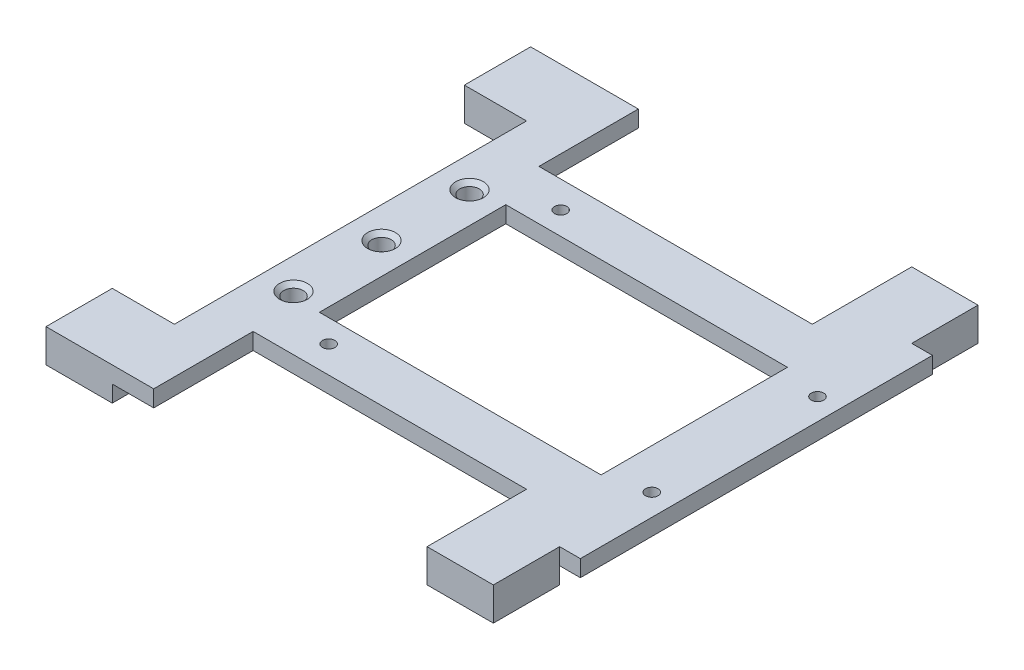
SolidWorks part; units mm, degrees
ref_plane "Front Plane" through (0, 0, 0) normal (0, 0, 1) x (1, 0, 0)
ref_plane "Top Plane" through (0, 0, 0) normal (0, 1, 0) x (1, 0, 0)
ref_plane "Right Plane" through (0, 0, 0) normal (1, 0, 0) x (0, 0, -1)
sketch "Sketch1" plane through (0, 0, 0) normal (0, 1, 0) x (1, 0, 0)
  line L1 (-56.5, 42.5) -> (56.5, 42.5)
  line L2 (-56.5, 42.5) -> (-56.5, -42.5)
  line L3 (-56.5, -42.5) -> (56.5, -42.5)
  line L4 (56.5, 42.5) -> (56.5, -42.5)
  line L5 (-56.5, 42.5) -> (56.5, -42.5) construction
  line L6 (-56.5, -42.5) -> (56.5, 42.5) construction
  point P0 (0, 0)
  dimension "D1" = 113
  dimension "D2" = 85
extrude "Boss-Extrude1" add sketch "Sketch1" along normal blind 4
sketch "Sketch2" plane through (0, 4, 0) normal (0, 1, 0) x (1, 0, 0)
  line L0 (0, 42.5) -> (0, -42.5) construction
  line L1 (56.5, 42.5) -> (-56.5, 42.5) construction
  line L2 (-56.5, -42.5) -> (56.5, -42.5) construction
  line L4 (-56.5, 0) -> (56.5, 0) construction
  line L5 (-56.5, 42.5) -> (-56.5, -42.5) construction
  line L6 (56.5, -42.5) -> (56.5, 42.5) construction
  circle A46 centre (-18.75, 28) radius 1.5
  circle A47 centre (-18.75, -28) radius 1.5
  circle A48 centre (51.25, -20) radius 1.5
  circle A49 centre (51.25, 20) radius 1.5
  point P20 (22.5, 0)
  line B0 (-25.4814, 0) -> (70.4814, 0) construction
  arc B1 (-19.5394, -30.8943) -> (-19.2077, -30.9649) centre (-18.75, -28) ccw construction
  arc B2 (-21.6443, -28.7894) -> (-19.5394, -30.8943) centre (-18.75, -28) ccw construction
  arc B3 (-21.7149, -28.4577) -> (-21.6443, -28.7894) centre (-18.75, -28) ccw construction
  arc B4 (-19.2077, 30.9649) -> (-19.5394, 30.8943) centre (-18.75, 28) ccw construction
  arc B5 (-19.5394, 30.8943) -> (-21.6443, 28.7894) centre (-18.75, 28) ccw construction
  arc B6 (-21.6443, 28.7894) -> (-21.7149, 28.4577) centre (-18.75, 28) ccw construction
  arc B7 (-21.7149, 28.4577) -> (-21.7149, -28.4577) centre (83.9083, 0) ccw construction
  arc B8 (-19.2077, -30.9649) -> (9.25, -34.7314) centre (9.25, 74.6583) ccw construction
  arc B9 (9.25, -34.7314) -> (63.3655, -15.1715) centre (9.25, 49.9083) ccw construction
  arc B10 (63.3655, -15.1715) -> (63.3655, 15.1715) centre (50.75, 0) ccw construction
  arc B11 (63.3655, 15.1715) -> (9.25, 34.7314) centre (9.25, -49.9083) ccw construction
  arc B12 (9.25, 34.7314) -> (-19.2077, 30.9649) centre (9.25, -74.6583) ccw construction
  arc B13 (51.25, 22.5132) -> (51.25, 17.4868) centre (51.25, 20) ccw construction
  arc B14 (51.25, 17.5) -> (51.25, 22.5) centre (51.25, 20) ccw construction
  arc B15 (51.25, -17.5) -> (51.25, -22.5) centre (51.25, -20) ccw construction
  arc B16 (51.25, -22.5132) -> (51.25, -17.4868) centre (51.25, -20) ccw construction
  arc B17 (-18.75, -25.5) -> (-18.75, -30.5) centre (-18.75, -28) ccw construction
  arc B18 (-18.75, -30.5132) -> (-18.75, -25.4868) centre (-18.75, -28) ccw construction
  arc B19 (-18.75, 30.5) -> (-18.75, 25.5) centre (-18.75, 28) ccw construction
  arc B20 (-18.75, 25.5) -> (-18.75, 30.5) centre (-18.75, 28) ccw construction
  dimension "D1" = 3
  dimension "D2" = 3
  dimension "D3" = 3
  dimension "D4" = 3
  dimension "D5" = 34
sketch_block_instance "Block2-1"
sketch_block "Block2"
extrude "Cut-Extrude1" cut sketch "Sketch2" against normal through all contours A46 | A49 | A47 | A48
sketch "Sketch4" plane through (0, 0, 0) normal (0, -1, 0) x (1, 0, 0)
  line L0 (-56.5, 42.5) -> (56.5, 42.5) construction
  line L5 (-56.5, 42.5) -> (-40.5, 42.5)
  line L6 (-56.5, 42.5) -> (-56.5, 58.5)
  line L7 (-56.5, 58.5) -> (-40.5, 58.5)
  line L8 (-40.5, 42.5) -> (-40.5, 58.5)
  line L9 (51.5, 42.5) -> (35.5, 42.5)
  line L10 (51.5, 42.5) -> (51.5, 58.5)
  line L11 (51.5, 58.5) -> (35.5, 58.5)
  line L12 (35.5, 42.5) -> (35.5, 58.5)
  line L18 (56.5, 42.5) -> (56.5, -42.5) construction
  line L19 (0, 0) -> (-56.5, 0) construction
  line L20 (-56.5, -42.5) -> (-56.5, 42.5) construction
  line L21 (51.5, -58.5) -> (35.5, -58.5)
  line L22 (35.5, -42.5) -> (35.5, -58.5)
  line L23 (51.5, -42.5) -> (35.5, -42.5)
  line L24 (51.5, -42.5) -> (51.5, -58.5)
  line L25 (-56.5, -58.5) -> (-40.5, -58.5)
  line L26 (-40.5, -42.5) -> (-40.5, -58.5)
  line L27 (-56.5, -42.5) -> (-40.5, -42.5)
  line L28 (-56.5, -42.5) -> (-56.5, -58.5)
  dimension "D1" = 16
  dimension "D2" = 16
  dimension "D3" = 5
  dimension "D4" = 16
  dimension "D5" = 16
extrude "Boss-Extrude3" add sketch "Sketch4" against normal up to surface (4 mm away) and the other way blind 1 up to face at (-18.75, 4, -26.5)
sketch "Sketch10" plane through (0, 4, 0) normal (0, 1, 0) x (1, 0, 0)
  line L0 (-40.5, -58.5) -> (-56.5, -58.5) construction
  line L1 (-40.5, -42.5) -> (-30.5, -42.5)
  line L2 (-40.5, -42.5) -> (-40.5, -58.5)
  line L3 (-40.5, -58.5) -> (-30.5, -58.5)
  line L4 (-30.5, -42.5) -> (-30.5, -58.5)
  line L5 (-40.5, 42.5) -> (-30.5, 42.5)
  line L6 (-40.5, 42.5) -> (-40.5, 58.5)
  line L7 (-40.5, 58.5) -> (-30.5, 58.5)
  line L8 (-30.5, 42.5) -> (-30.5, 58.5)
  line L9 (-56.5, 58.5) -> (-40.5, 58.5) construction
  dimension "D1" = 10
  dimension "D2" = 10
extrude "Boss-Extrude6" add sketch "Sketch10" against normal up to surface (4 mm away) up to face at (-18.75, 0, -26.5)
sketch "Sketch6" plane through (0, 4, 0) normal (0, 1, 0) x (1, 0, 0)
  line L0 (35.5, 42.5) -> (35.5, 58.5) construction
  line L1 (-26.5, 22.5) -> (41.5, 22.5)
  line L2 (-26.5, 22.5) -> (-26.5, -22.5)
  line L3 (-26.5, -22.5) -> (41.5, -22.5)
  line L4 (41.5, 22.5) -> (41.5, -22.5)
  line L5 (35.5, -58.5) -> (35.5, -42.5) construction
  line L6 (35.5, 42.5) -> (-30.5, 42.5) construction
  line L7 (-30.5, -42.5) -> (35.5, -42.5) construction
  line L8 (-56.5, 58.5) -> (-56.5, -58.5) construction
  line L9 (-41.5, 0) -> (-56.5, 0) construction
  line L10 (-56.5, 42.5) -> (-41.5, 42.5)
  line L11 (-56.5, 42.5) -> (-56.5, -42.5)
  line L12 (-56.5, -42.5) -> (-41.5, -42.5)
  line L13 (-41.5, 42.5) -> (-41.5, -42.5)
  line L14 (-26.5, 0) -> (41.5, 0) construction
  line L15 (-30.5, 42.5) -> (35.5, 42.5)
  line L16 (-30.5, 42.5) -> (-30.5, 34.5)
  line L17 (-30.5, 34.5) -> (35.5, 34.5)
  line L18 (35.5, 42.5) -> (35.5, 34.5)
  line L19 (-30.5, -42.5) -> (35.5, -42.5)
  line L20 (-30.5, -42.5) -> (-30.5, -34.5)
  line L21 (-30.5, -34.5) -> (35.5, -34.5)
  line L22 (35.5, -42.5) -> (35.5, -34.5)
  line L23 (56.5, -42.5) -> (56.5, 42.5) construction
  dimension "D1" = 20
  dimension "D2" = 20
  dimension "D3" = 30
  dimension "D4" = 15
  dimension "D5" = 85
  dimension "D6" = 8
  dimension "D7" = 8
  dimension "D8" = 15
extrude "Cut-Extrude2" cut sketch "Sketch6" against normal through all
sketch "Sketch8" plane through (0, -1, 0) normal (0, -1, 0) x (1, 0, 0)
  line L0 (-56.5, 58.5) -> (-40.5, 58.5) construction
  line L1 (-56.5, 58.5) -> (-56.5, 42.5) construction
  line L2 (-56.5, 42.5) -> (-40.5, 42.5) construction
  line L3 (-40.5, 58.5) -> (-40.5, 42.5) construction
  line L4 (35.5, 58.5) -> (51.5, 58.5) construction
  line L5 (35.5, 58.5) -> (35.5, 42.5) construction
  line L6 (35.5, 42.5) -> (51.5, 42.5) construction
  line L7 (51.5, 58.5) -> (51.5, 42.5) construction
  line L8 (-56.5, 58.5) -> (-40.5, 42.5) construction
  line L9 (-56.5, 42.5) -> (-40.5, 58.5) construction
  line L10 (35.5, 58.5) -> (51.5, 42.5) construction
  line L11 (35.5, 42.5) -> (51.5, 58.5) construction
  line L12 (51.5, 58.5) -> (35.5, 58.5) construction
  line L13 (0, 0) -> (-56.5, 0) construction
  line L14 (-56.5, 42.5) -> (-40.5, 42.5) construction
  line L15 (35.5, 42.5) -> (51.5, 42.5) construction
  circle A0 centre (-48.5, 50.5) radius 6.1
  circle A1 centre (43.5, 50.5) radius 6.1
  circle A2 centre (43.5, -50.5) radius 6.1
  circle A3 centre (-48.5, -50.5) radius 6.1
  dimension "D3" = 12.2
  dimension "D4" = 12.2
extrude "Cut-Extrude3" cut sketch "Sketch8" against normal blind 3.2
sketch "Sketch9" plane through (0, -1, 0) normal (0, -1, 0) x (1, 0, 0)
  line L0 (-55.5, 57.5) -> (-55.5, 43.5)
  line L1 (-56.5, 58.5) -> (-40.5, 58.5)
  line L2 (-56.5, 58.5) -> (-56.5, 42.5)
  line L3 (-56.5, 42.5) -> (-40.5, 42.5)
  line L4 (-40.5, 58.5) -> (-40.5, 42.5)
  line L5 (35.5, 58.5) -> (51.5, 58.5)
  line L6 (35.5, 58.5) -> (35.5, 42.5)
  line L7 (35.5, 42.5) -> (51.5, 42.5)
  line L8 (51.5, 58.5) -> (51.5, 42.5)
  line L9 (-55.5, 43.5) -> (-41.5, 43.5)
  line L10 (-41.5, 57.5) -> (-41.5, 43.5)
  line L11 (-55.5, 57.5) -> (-41.5, 57.5)
  line L16 (0, 0) -> (-56.5, 0) construction
  line L17 (36.5, -43.5) -> (50.5, -43.5)
  line L18 (36.5, -57.5) -> (36.5, -43.5)
  line L19 (50.5, -57.5) -> (36.5, -57.5)
  line L20 (50.5, 43.5) -> (50.5, 57.5)
  line L21 (50.5, 57.5) -> (36.5, 57.5)
  line L22 (36.5, 57.5) -> (36.5, 43.5)
  line L23 (36.5, 43.5) -> (50.5, 43.5)
  line L24 (50.5, 43.5) -> (50.5, 57.5)
  line L25 (50.5, 57.5) -> (36.5, 57.5)
  line L26 (36.5, 57.5) -> (36.5, 43.5)
  line L27 (36.5, 43.5) -> (50.5, 43.5)
  line L28 (50.5, -43.5) -> (50.5, -57.5)
  line L29 (-55.5, -57.5) -> (-41.5, -57.5)
  line L30 (-41.5, -57.5) -> (-41.5, -43.5)
  line L31 (-55.5, -43.5) -> (-41.5, -43.5)
  line L32 (51.5, -58.5) -> (51.5, -42.5)
  line L33 (35.5, -42.5) -> (51.5, -42.5)
  line L34 (35.5, -58.5) -> (35.5, -42.5)
  line L35 (35.5, -58.5) -> (51.5, -58.5)
  line L36 (-40.5, -58.5) -> (-40.5, -42.5)
  line L37 (-56.5, -42.5) -> (-40.5, -42.5)
  line L38 (-56.5, -58.5) -> (-56.5, -42.5)
  line L39 (-56.5, -58.5) -> (-40.5, -58.5)
  line L40 (-55.5, -57.5) -> (-55.5, -43.5)
  dimension "D1" = 1
  dimension "D2" = 1
extrude "Boss-Extrude5" add sketch "Sketch9" along normal blind 3
fillet "Fillet1" radius 0.2 4 edges at (43.5, -1, -44.4) (-48.5, -1, -44.4) (43.5, -1, 44.4) (-48.5, -1, 44.4)
sketch "Sketch11" plane through (0, 4, 0) normal (0, 1, 0) x (1, 0, 0)
  line L1 (-41.5, 42.5) -> (-26.5, 42.5) construction
  line L2 (-41.5, 42.5) -> (-41.5, -42.5) construction
  line L3 (-41.5, -42.5) -> (-26.5, -42.5) construction
  line L4 (-26.5, 42.5) -> (-26.5, -42.5) construction
  line L5 (-56.5, -42.5) -> (-41.5, -42.5) construction
  line L6 (-34, 21.25) -> (-34, 42.5) construction
  line L7 (-34, 21.25) -> (-34, 0) construction
  line L8 (-34, 0) -> (-34, -21.25) construction
  line L9 (-34, -21.25) -> (-34, -42.5) construction
  line L10 (-26.5, 22.5) -> (-26.5, -22.5) construction
  circle A0 centre (-34, 21.25) radius 2.35
  circle A1 centre (-34, 0) radius 2.35
  circle A2 centre (-34, -21.25) radius 2.35
  dimension "D1" = 4.7
  dimension "D2" = 4.7
  dimension "D3" = 4.7
extrude "Cut-Extrude4" cut sketch "Sketch11" against normal blind 4
chamfer "Chamfer1" distance 1 angle 45 3 edges at (-34, 4, -18.9) (-34, 4, 2.35) (-34, 4, 23.6)
